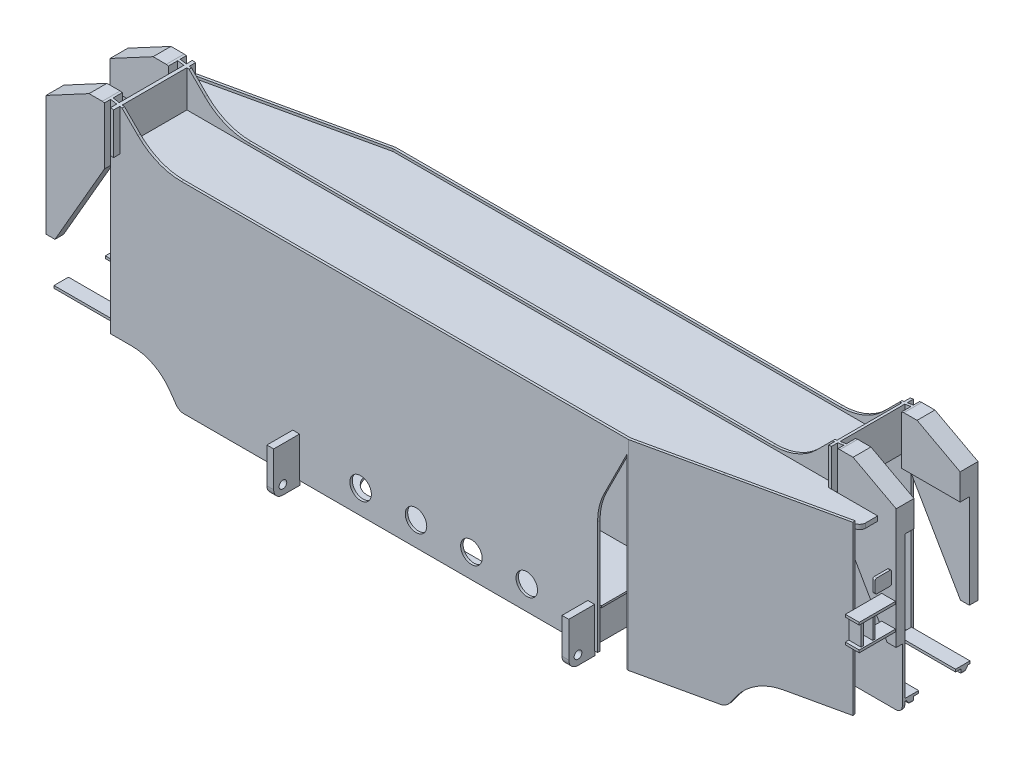
SolidWorks part; units mm, degrees
ref_plane "正面" through (0, 0, 0) normal (0, 0, 1) x (1, 0, 0)
ref_plane "平面" through (0, 0, 0) normal (0, 1, 0) x (1, 0, 0)
ref_plane "右側面" through (0, 0, 0) normal (1, 0, 0) x (0, 0, -1)
ref_plane "平面1" through (0, 0, 238) normal (0, 0, 1) x (1, 0, 0)
sketch "ｽｹｯﾁ2" plane through (0, 0, 238) normal (0, 0, 1) x (1, 0, 0)
  line L0 (20, 120) -> (259.781, 119.9998)
  line L1 (382.7741, 55.8641) -> (403.0452, 26.8271)
  line L2 (427.644, 13.9998) -> (2117.356, 13.9998)
  line L3 (2141.9548, 26.8271) -> (2162.2259, 55.8641)
  line L4 (2285.219, 119.9998) -> (2525, 120)
  line L5 (2545, 140) -> (2545, 315.36)
  line L6 (2545, 315.36) -> (2545, 706)
  line L7 (2545, 706) -> (2405, 781)
  line L8 (2405, 781) -> (2362, 781)
  line L9 (2362, 781) -> (2318, 774)
  line L10 (2318, 774) -> (2266.5789, 722.5791)
  line L11 (2125.157, 663.9999) -> (419.843, 663.9999)
  line L12 (278.4211, 722.5791) -> (227, 774)
  line L13 (227, 774) -> (183, 781)
  line L14 (183, 781) -> (140, 781)
  line L15 (140, 781) -> (0, 706)
  line L16 (0, 706) -> (0, 315.36)
  line L17 (0, 315.36) -> (0, 140)
  arc A0 (0, 140) -> (20, 120) centre (20, 140) ccw
  arc A1 (259.781, 119.9998) -> (382.7741, 55.8641) centre (259.781, -30) cw
  arc A2 (403.0452, 26.8271) -> (427.644, 13.9998) centre (427.644, 44) ccw
  arc A3 (2117.356, 13.9998) -> (2141.9548, 26.8271) centre (2117.356, 44) ccw
  arc A4 (2162.2259, 55.8641) -> (2285.219, 119.9998) centre (2285.219, -30) cw
  arc A5 (2525, 120) -> (2545, 140) centre (2525, 140) ccw
  arc A6 (2266.5789, 722.5791) -> (2125.157, 663.9999) centre (2125.157, 864) cw
  arc A7 (419.843, 663.9999) -> (278.4211, 722.5791) centre (419.843, 864) cw
extrude "ﾎﾞｽ - 押し出し1" add sketch "ｽｹｯﾁ2" along normal blind 8
sketch "ｽｹｯﾁ3" plane through (0, 0, 238) normal (0, 0, 1) x (1, 0, 0)
  line L0 (1072.5, 297) -> (1472.5, 297)
  line L1 (1472.5, 497) -> (1072.5, 497)
  circle A0 centre (972.5, 92) radius 35
  circle A1 centre (1272.5, 92) radius 35
  circle A2 centre (1572.5, 92) radius 35
  arc A3 (1472.5, 297) -> (1572.5, 397) centre (1472.5, 397) ccw
  arc A4 (1572.5, 397) -> (1472.5, 497) centre (1472.5, 397) ccw
  arc A5 (1072.5, 497) -> (972.5, 397) centre (1072.5, 397) ccw
  arc A6 (972.5, 397) -> (1072.5, 297) centre (1072.5, 397) ccw
  circle A7 centre (50, 499) radius 20.25
  circle A8 centre (2495, 499) radius 20.25
  circle A9 centre (27, 401.5) radius 10.5
  circle A10 centre (2518, 401.5) radius 10.5
sketch "ｽｹｯﾁ4" plane through (0, 0, 238) normal (0, 0, 1) x (1, 0, 0)
  line L0 (1072.5, 297) -> (1472.5, 297)
  line L1 (1472.5, 497) -> (1072.5, 497)
  circle A0 centre (972.5, 92) radius 35
  circle A1 centre (1272.5, 92) radius 35
  circle A2 centre (1572.5, 92) radius 35
  arc A3 (1472.5, 297) -> (1572.5, 397) centre (1472.5, 397) ccw
  arc A4 (1572.5, 397) -> (1472.5, 497) centre (1472.5, 397) ccw
  arc A5 (1072.5, 497) -> (972.5, 397) centre (1072.5, 397) ccw
  arc A6 (972.5, 397) -> (1072.5, 297) centre (1072.5, 397) ccw
  circle A7 centre (50, 499) radius 20.25
  circle A8 centre (2495, 499) radius 20.25
  circle A9 centre (27, 401.5) radius 10.5
  circle A10 centre (2518, 401.5) radius 10.5
extrude "ｶｯﾄ - 押し出し2" cut sketch "ｽｹｯﾁ4" along normal blind 8
ref_plane "平面2" through (0, 0, 20) normal (0, 0, 1) x (1, 0, 0)
sketch "ｽｹｯﾁ6" plane through (0, 0, 20) normal (0, 0, 1) x (1, 0, 0)
  line L0 (772.5, 14) -> (2117.356, 13.9998)
  line L1 (2141.9548, 26.8271) -> (2162.2259, 55.8641)
  line L2 (2285.219, 119.9998) -> (2355, 120)
  line L3 (2355, 120) -> (2355, 779.8864)
  line L4 (2355, 779.8864) -> (2318, 774)
  line L5 (2318, 774) -> (2266.5789, 722.5791)
  line L6 (2125.157, 663.9999) -> (672.5, 664)
  line L7 (672.5, 664) -> (672.5, 629)
  line L8 (672.5, 629) -> (751.3851, 471.2291)
  line L9 (772.4999, 381.786) -> (772.5, 14)
  arc A0 (2117.356, 13.9998) -> (2141.9548, 26.8271) centre (2117.356, 44) ccw
  arc A1 (2162.2259, 55.8641) -> (2285.219, 119.9998) centre (2285.219, -30) cw
  arc A2 (2266.5789, 722.5791) -> (2125.157, 663.9999) centre (2125.157, 864) cw
  arc A3 (751.3851, 471.2291) -> (772.4999, 381.786) centre (572.5, 381.786) cw
extrude "ﾎﾞｽ - 押し出し2" add sketch "ｽｹｯﾁ6" along normal blind 8
sketch "ｽｹｯﾁ7" plane through (0, 0, 20) normal (0, 0, 1) x (1, 0, 0)
  circle A0 centre (1002.5, 92) radius 35
  circle A1 centre (1182.5, 92) radius 35
  circle A2 centre (1362.5, 92) radius 35
  circle A3 centre (1542.5, 92) radius 35
sketch "ｽｹｯﾁ8" plane through (0, 0, 20) normal (0, 0, 1) x (1, 0, 0)
  circle A0 centre (1002.5, 92) radius 35
  circle A1 centre (1182.5, 92) radius 35
  circle A2 centre (1362.5, 92) radius 35
  circle A3 centre (1542.5, 92) radius 35
extrude "ｶｯﾄ - 押し出し4" cut sketch "ｽｹｯﾁ8" along normal blind 8
ref_plane "平面3" through (0, 0, 456) normal (0, 0, 1) x (1, 0, 0)
sketch "ｽｹｯﾁ10" plane through (0, 0, 456) normal (0, 0, 1) x (1, 0, 0)
  line L0 (1772.5, 14) -> (1772.5001, 381.786)
  line L1 (1793.6149, 471.2291) -> (1872.5, 629)
  line L2 (1872.5, 629) -> (1872.5, 664)
  line L3 (1872.5, 664) -> (419.843, 663.9999)
  line L4 (278.4211, 722.5791) -> (227, 774)
  line L5 (227, 774) -> (190, 779.8864)
  line L6 (190, 779.8864) -> (190, 120)
  line L7 (190, 120) -> (259.781, 119.9998)
  line L8 (382.7741, 55.8641) -> (403.0452, 26.8271)
  line L9 (427.644, 13.9998) -> (1772.5, 14)
  arc A0 (1772.5001, 381.786) -> (1793.6149, 471.2291) centre (1972.5, 381.786) cw
  arc A1 (419.843, 663.9999) -> (278.4211, 722.5791) centre (419.843, 864) cw
  arc A2 (259.781, 119.9998) -> (382.7741, 55.8641) centre (259.781, -30) cw
  arc A3 (403.0452, 26.8271) -> (427.644, 13.9998) centre (427.644, 44) ccw
extrude "ﾎﾞｽ - 押し出し3" add sketch "ｽｹｯﾁ10" along normal blind 8
sketch "ｽｹｯﾁ11" plane through (0, 0, 456) normal (0, 0, 1) x (1, 0, 0)
  circle A0 centre (1002.5, 92) radius 35
  circle A1 centre (1182.5, 92) radius 35
  circle A2 centre (1362.5, 92) radius 35
  circle A3 centre (1542.5, 92) radius 35
sketch "ｽｹｯﾁ12" plane through (0, 0, 456) normal (0, 0, 1) x (1, 0, 0)
  circle A0 centre (1002.5, 92) radius 35
  circle A1 centre (1182.5, 92) radius 35
  circle A2 centre (1362.5, 92) radius 35
  circle A3 centre (1542.5, 92) radius 35
extrude "ｶｯﾄ - 押し出し6" cut sketch "ｽｹｯﾁ12" along normal blind 8
ref_plane "平面4" through (0, 14, 0) normal (0, 1, 0) x (1, 0, 0)
sketch "ｽｹｯﾁ14" plane through (0, 14, 0) normal (0, 1, 0) x (1, 0, 0)
  line L0 (678.3594, -26.7085) -> (75.7, -159.54)
  line L1 (75.7, -159.54) -> (73.9781, -151.7275)
  line L2 (73.9781, -151.7275) -> (671.6288, -20)
  line L3 (671.6288, -20) -> (676.8807, -20)
  line L4 (676.8807, -20) -> (678.3594, -26.7085)
extrude "ﾎﾞｽ - 押し出し4" add sketch "ｽｹｯﾁ14" along normal blind 650
sketch "ｽｹｯﾁ15" plane through (0, 14, 0) normal (0, 1, 0) x (1, 0, 0)
  line L0 (1866.6406, -457.2915) -> (2469.3, -324.46)
  line L1 (2469.3, -324.46) -> (2471.0219, -332.2725)
  line L2 (2471.0219, -332.2725) -> (1873.3712, -464)
  line L3 (1873.3712, -464) -> (1868.1193, -464)
  line L4 (1868.1193, -464) -> (1866.6406, -457.2915)
extrude "ﾎﾞｽ - 押し出し5" add sketch "ｽｹｯﾁ15" along normal blind 650
ref_plane "平面5" through (0, 641, 0) normal (0, 1, 0) x (1, 0, 0)
sketch "ｽｹｯﾁ17" plane through (0, 641, 0) normal (0, 1, 0) x (1, 0, 0)
  line L0 (672.5, -28) -> (75.7206, -159.5325)
  line L1 (59.9974, -179.072) -> (60, -218)
  line L2 (60, -218) -> (220, -218)
  line L3 (220, -218) -> (220, -238)
  line L4 (220, -238) -> (2325, -238)
  line L5 (2325, -238) -> (2325, -28)
  line L6 (2325, -28) -> (672.5, -28)
  arc A0 (75.7206, -159.5325) -> (59.9974, -179.072) centre (80, -179.072) ccw
extrude "ﾎﾞｽ - 押し出し6" add sketch "ｽｹｯﾁ17" along normal blind 15
sketch "ｽｹｯﾁ18" plane through (0, 641, 0) normal (0, 1, 0) x (1, 0, 0)
  line L0 (1872.5, -456) -> (2469.2794, -324.4675)
  line L1 (2485.0026, -304.928) -> (2485, -266)
  line L2 (2485, -266) -> (2325, -266)
  line L3 (2325, -266) -> (2325, -246)
  line L4 (2325, -246) -> (220, -246)
  line L5 (220, -246) -> (220, -456)
  line L6 (220, -456) -> (1872.5, -456)
  arc A0 (2469.2794, -324.4675) -> (2485.0026, -304.928) centre (2465, -304.928) ccw
extrude "ﾎﾞｽ - 押し出し7" add sketch "ｽｹｯﾁ18" along normal blind 15
ref_plane "平面6" through (0, 22, 0) normal (0, 1, 0) x (1, 0, 0)
sketch "ｽｹｯﾁ20" plane through (0, 22, 0) normal (0, 1, 0) x (1, 0, 0)
  line L0 (804, -28) -> (2098.5, -28)
  line L1 (2098.5, -28) -> (2098.5, -238)
  line L2 (2098.5, -238) -> (804, -238)
  line L3 (804, -238) -> (804, -28)
extrude "ﾎﾞｽ - 押し出し8" add sketch "ｽｹｯﾁ20" along normal blind 8
sketch "ｽｹｯﾁ21" plane through (0, 22, 0) normal (0, 1, 0) x (1, 0, 0)
  line L0 (1202, -73) -> (1342, -73)
  line L1 (1342, -193) -> (1202, -193)
  circle A0 centre (972, -133) radius 60
  circle A1 centre (1572, -133) radius 60
  circle A2 centre (1942, -133) radius 60
  arc A3 (1342, -73) -> (1402, -133) centre (1342, -133) cw
  arc A4 (1402, -133) -> (1342, -193) centre (1342, -133) cw
  arc A5 (1202, -193) -> (1142, -133) centre (1202, -133) cw
  arc A6 (1142, -133) -> (1202, -73) centre (1202, -133) cw
sketch "ｽｹｯﾁ22" plane through (0, 22, 0) normal (0, 1, 0) x (1, 0, 0)
  line L0 (1202, -73) -> (1342, -73)
  line L1 (1342, -193) -> (1202, -193)
  circle A0 centre (972, -133) radius 60
  circle A1 centre (1572, -133) radius 60
  circle A2 centre (1942, -133) radius 60
  arc A3 (1342, -73) -> (1402, -133) centre (1342, -133) cw
  arc A4 (1402, -133) -> (1342, -193) centre (1342, -133) cw
  arc A5 (1202, -193) -> (1142, -133) centre (1202, -133) cw
  arc A6 (1142, -133) -> (1202, -73) centre (1202, -133) cw
extrude "ｶｯﾄ - 押し出し8" cut sketch "ｽｹｯﾁ22" along normal blind 8
sketch "ｽｹｯﾁ23" plane through (0, 22, 0) normal (0, 1, 0) x (1, 0, 0)
  line L0 (446.5, -246) -> (1741, -246)
  line L1 (1741, -246) -> (1741, -456)
  line L2 (1741, -456) -> (446.5, -456)
  line L3 (446.5, -456) -> (446.5, -246)
extrude "ﾎﾞｽ - 押し出し9" add sketch "ｽｹｯﾁ23" along normal blind 8
sketch "ｽｹｯﾁ24" plane through (0, 22, 0) normal (0, 1, 0) x (1, 0, 0)
  line L0 (1203, -291) -> (1343, -291)
  line L1 (1343, -411) -> (1203, -411)
  circle A0 centre (603, -351) radius 60
  circle A1 centre (973, -351) radius 60
  circle A2 centre (1573, -351) radius 60
  arc A3 (1343, -291) -> (1403, -351) centre (1343, -351) cw
  arc A4 (1403, -351) -> (1343, -411) centre (1343, -351) cw
  arc A5 (1203, -411) -> (1143, -351) centre (1203, -351) cw
  arc A6 (1143, -351) -> (1203, -291) centre (1203, -351) cw
extrude "ｶｯﾄ - 押し出し9" cut sketch "ｽｹｯﾁ24" along normal blind 8
ref_plane "平面7" through (0, 138, 0) normal (0, 1, 0) x (1, 0, 0)
sketch "ｽｹｯﾁ26" plane through (0, 138, 0) normal (0, 1, 0) x (1, 0, 0)
  line L0 (768, -28) -> (1712, -28)
  line L1 (1712, -28) -> (1712, -238)
  line L2 (1712, -238) -> (768, -238)
  line L3 (768, -238) -> (768, -28)
extrude "ﾎﾞｽ - 押し出し10" add sketch "ｽｹｯﾁ26" along normal blind 6
sketch "ｽｹｯﾁ27" plane through (0, 138, 0) normal (0, 1, 0) x (1, 0, 0)
  line L0 (833, -246) -> (1777, -246)
  line L1 (1777, -246) -> (1777, -456)
  line L2 (1777, -456) -> (833, -456)
  line L3 (833, -456) -> (833, -246)
extrude "ﾎﾞｽ - 押し出し11" add sketch "ｽｹｯﾁ27" along normal blind 6
ref_plane "平面8" through (0, 0, 218) normal (0, 0, 1) x (1, 0, 0)
sketch "ｽｹｯﾁ29" plane through (0, 0, 218) normal (0, 0, 1) x (1, 0, 0)
  line L0 (0, 315.36) -> (29.1052, 315.36)
  line L1 (29.1052, 315.36) -> (190, 594.038)
  line L2 (190, 594.038) -> (190, 779.8864)
  line L3 (190, 779.8864) -> (183, 781)
  line L4 (183, 781) -> (140, 781)
  line L5 (140, 781) -> (0, 706)
  line L6 (0, 706) -> (0, 315.36)
extrude "ﾎﾞｽ - 押し出し12" add sketch "ｽｹｯﾁ29" along normal blind 20
ref_plane "平面9" through (0, 0, 464) normal (0, 0, 1) x (1, 0, 0)
sketch "ｽｹｯﾁ31" plane through (0, 0, 464) normal (0, 0, 1) x (1, 0, 0)
  line L0 (0, 315.36) -> (29.1052, 315.36)
  line L1 (29.1052, 315.36) -> (190, 594.038)
  line L2 (190, 594.038) -> (190, 779.8864)
  line L3 (190, 779.8864) -> (183, 781)
  line L4 (183, 781) -> (140, 781)
  line L5 (140, 781) -> (0, 706)
  line L6 (0, 706) -> (0, 315.36)
extrude "ﾎﾞｽ - 押し出し13" add sketch "ｽｹｯﾁ31" along normal blind 20
sketch "ｽｹｯﾁ32" plane through (0, 0, 0) normal (0, 0, 1) x (1, 0, 0)
  line L0 (2545, 315.36) -> (2545, 706)
  line L1 (2545, 706) -> (2405, 781)
  line L2 (2405, 781) -> (2362, 781)
  line L3 (2362, 781) -> (2355, 779.8864)
  line L4 (2355, 779.8864) -> (2355, 594.038)
  line L5 (2355, 594.038) -> (2515.8948, 315.36)
  line L6 (2515.8948, 315.36) -> (2545, 315.36)
extrude "ﾎﾞｽ - 押し出し14" add sketch "ｽｹｯﾁ32" along normal blind 20
ref_plane "平面10" through (0, 0, 246) normal (0, 0, 1) x (1, 0, 0)
sketch "ｽｹｯﾁ34" plane through (0, 0, 246) normal (0, 0, 1) x (1, 0, 0)
  line L0 (2545, 315.36) -> (2545, 706)
  line L1 (2545, 706) -> (2405, 781)
  line L2 (2405, 781) -> (2362, 781)
  line L3 (2362, 781) -> (2355, 779.8864)
  line L4 (2355, 779.8864) -> (2355, 594.038)
  line L5 (2355, 594.038) -> (2515.8948, 315.36)
  line L6 (2515.8948, 315.36) -> (2545, 315.36)
extrude "ﾎﾞｽ - 押し出し15" add sketch "ｽｹｯﾁ34" along normal blind 20
sketch "ｽｹｯﾁ35" plane through (0, 0, 20) normal (0, 0, 1) x (1, 0, 0)
  line L0 (2545, 315.36) -> (2545, 706)
  line L1 (2545, 706) -> (2405, 781)
  line L2 (2405, 781) -> (2362, 781)
  line L3 (2362, 781) -> (2355, 779.8864)
  line L4 (2355, 779.8864) -> (2355, 594.038)
  line L5 (2355, 594.038) -> (2515.8948, 315.36)
  line L6 (2515.8948, 315.36) -> (2545, 315.36)
extrude "ﾎﾞｽ - 押し出し16" add sketch "ｽｹｯﾁ35" along normal blind 8
sketch "ｽｹｯﾁ36" plane through (0, 0, 456) normal (0, 0, 1) x (1, 0, 0)
  line L0 (0, 315.36) -> (29.1052, 315.36)
  line L1 (29.1052, 315.36) -> (190, 594.038)
  line L2 (190, 594.038) -> (190, 779.8864)
  line L3 (190, 779.8864) -> (183, 781)
  line L4 (183, 781) -> (140, 781)
  line L5 (140, 781) -> (0, 706)
  line L6 (0, 706) -> (0, 315.36)
extrude "ﾎﾞｽ - 押し出し17" add sketch "ｽｹｯﾁ36" along normal blind 8
sketch "ｽｹｯﾁ37" plane through (0, 0, 246) normal (0, 0, 1) x (1, 0, 0)
  line L0 (0, 620.82) -> (190, 620.82)
  line L1 (190, 620.82) -> (190, 779.8864)
  line L2 (190, 779.8864) -> (183, 781)
  line L3 (183, 781) -> (140, 781)
  line L4 (140, 781) -> (0, 706)
  line L5 (0, 706) -> (0, 620.82)
extrude "ﾎﾞｽ - 押し出し18" add sketch "ｽｹｯﾁ37" along normal blind 30
ref_plane "平面11" through (0, 0, 426) normal (0, 0, 1) x (1, 0, 0)
sketch "ｽｹｯﾁ39" plane through (0, 0, 426) normal (0, 0, 1) x (1, 0, 0)
  line L0 (0, 620.82) -> (190, 620.82)
  line L1 (190, 620.82) -> (190, 779.8864)
  line L2 (190, 779.8864) -> (183, 781)
  line L3 (183, 781) -> (140, 781)
  line L4 (140, 781) -> (0, 706)
  line L5 (0, 706) -> (0, 620.82)
extrude "ﾎﾞｽ - 押し出し19" add sketch "ｽｹｯﾁ39" along normal blind 30
ref_plane "平面12" through (0, 0, 28) normal (0, 0, 1) x (1, 0, 0)
sketch "ｽｹｯﾁ41" plane through (0, 0, 28) normal (0, 0, 1) x (1, 0, 0)
  line L0 (2545, 620.82) -> (2545, 706)
  line L1 (2545, 706) -> (2405, 781)
  line L2 (2405, 781) -> (2362, 781)
  line L3 (2362, 781) -> (2355, 779.8864)
  line L4 (2355, 779.8864) -> (2355, 620.82)
  line L5 (2355, 620.82) -> (2545, 620.82)
extrude "ﾎﾞｽ - 押し出し20" add sketch "ｽｹｯﾁ41" along normal blind 30
ref_plane "平面13" through (0, 0, 208) normal (0, 0, 1) x (1, 0, 0)
sketch "ｽｹｯﾁ43" plane through (0, 0, 208) normal (0, 0, 1) x (1, 0, 0)
  line L0 (2545, 620.82) -> (2545, 706)
  line L1 (2545, 706) -> (2405, 781)
  line L2 (2405, 781) -> (2362, 781)
  line L3 (2362, 781) -> (2355, 779.8864)
  line L4 (2355, 779.8864) -> (2355, 620.82)
  line L5 (2355, 620.82) -> (2545, 620.82)
extrude "ﾎﾞｽ - 押し出し21" add sketch "ｽｹｯﾁ43" along normal blind 30
sketch "ｽｹｯﾁ44" plane through (0, 0, 0) normal (1, 0, 0) x (0, 0, -1)
  line L0 (-251.6, 150) -> (-450.4, 150)
  line L1 (-450.4, 150) -> (-450.4, 149)
  line L2 (-450.4, 149) -> (-442.698, 138)
  line L3 (-442.698, 138) -> (-259.302, 138)
  line L4 (-259.302, 138) -> (-251.6, 149)
  line L5 (-251.6, 149) -> (-251.6, 150)
extrude "ﾎﾞｽ - 押し出し22" add sketch "ｽｹｯﾁ44" along normal blind 346.3065
sketch "ｽｹｯﾁ45" plane through (0, 138, 0) normal (0, 1, 0) x (1, 0, 0)
  line L0 (-10, -273.771) -> (155, -273.771)
  line L1 (195, -313.771) -> (195, -388.229)
  line L2 (155, -428.229) -> (-10, -428.229)
  line L3 (-10, -428.229) -> (-10, -273.771)
  arc A0 (155, -273.771) -> (195, -313.771) centre (155, -313.771) cw
  arc A1 (195, -388.229) -> (155, -428.229) centre (155, -388.229) cw
sketch "ｽｹｯﾁ46" plane through (0, 138, 0) normal (0, 1, 0) x (1, 0, 0)
  line L0 (-10, -273.771) -> (155, -273.771)
  line L1 (195, -313.771) -> (195, -388.229)
  line L2 (155, -428.229) -> (-10, -428.229)
  line L3 (-10, -428.229) -> (-10, -273.771)
  arc A0 (155, -273.771) -> (195, -313.771) centre (155, -313.771) cw
  arc A1 (195, -388.229) -> (155, -428.229) centre (155, -388.229) cw
extrude "ｶｯﾄ - 押し出し11" cut sketch "ｽｹｯﾁ46" along normal blind 12
ref_plane "平面14" through (2545, 0, 0) normal (1, 0, 0) x (0, 0, -1)
sketch "ｽｹｯﾁ48" plane through (2545, 0, 0) normal (1, 0, 0) x (0, 0, -1)
  line L0 (-232.4, 150) -> (-232.4, 149)
  line L1 (-232.4, 149) -> (-224.698, 138)
  line L2 (-224.698, 138) -> (-41.302, 138)
  line L3 (-41.302, 138) -> (-33.6, 149)
  line L4 (-33.6, 149) -> (-33.6, 150)
  line L5 (-33.6, 150) -> (-232.4, 150)
extrude "ﾎﾞｽ - 押し出し23" add sketch "ｽｹｯﾁ48" against normal blind 346.3065
sketch "ｽｹｯﾁ49" plane through (0, 138, 0) normal (0, 1, 0) x (1, 0, 0)
  line L0 (2555, -210.229) -> (2390, -210.229)
  line L1 (2350, -170.229) -> (2350, -95.771)
  line L2 (2390, -55.771) -> (2555, -55.771)
  line L3 (2555, -55.771) -> (2555, -210.229)
  arc A0 (2390, -210.229) -> (2350, -170.229) centre (2390, -170.229) cw
  arc A1 (2350, -95.771) -> (2390, -55.771) centre (2390, -95.771) cw
extrude "ｶｯﾄ - 押し出し12" cut sketch "ｽｹｯﾁ49" along normal blind 12
ref_plane "平面15" through (0, 150, 0) normal (0, 1, 0) x (1, 0, 0)
sketch "ｽｹｯﾁ51" plane through (0, 150, 0) normal (0, 1, 0) x (1, 0, 0)
  line L0 (0, -244) -> (190, -244)
  line L1 (190, -244) -> (190, -291)
  line L2 (190, -291) -> (0, -291)
  line L3 (0, -291) -> (0, -244)
  line L4 (0, -411) -> (190, -411)
  line L5 (190, -411) -> (190, -458)
  line L6 (190, -458) -> (0, -458)
  line L7 (0, -458) -> (0, -411)
  line L8 (215.708, -244) -> (833, -244)
  line L9 (833, -244) -> (833, -291)
  line L10 (833, -291) -> (215.708, -291)
  line L11 (215.708, -291) -> (215.708, -244)
  line L12 (215.708, -411) -> (833, -411)
  line L13 (833, -411) -> (833, -458)
  line L14 (833, -458) -> (215.708, -458)
  line L15 (215.708, -458) -> (215.708, -411)
extrude "ﾎﾞｽ - 押し出し24" add sketch "ｽｹｯﾁ51" along normal blind 8
sketch "ｽｹｯﾁ52" plane through (0, 150, 0) normal (0, 1, 0) x (1, 0, 0)
  line L0 (1712, -193) -> (2329.292, -193)
  line L1 (2329.292, -193) -> (2329.292, -240)
  line L2 (2329.292, -240) -> (1712, -240)
  line L3 (1712, -240) -> (1712, -193)
  line L4 (1712, -26) -> (2329.292, -26)
  line L5 (2329.292, -26) -> (2329.292, -73)
  line L6 (2329.292, -73) -> (1712, -73)
  line L7 (1712, -73) -> (1712, -26)
  line L8 (2355, -193) -> (2545, -193)
  line L9 (2545, -193) -> (2545, -240)
  line L10 (2545, -240) -> (2355, -240)
  line L11 (2355, -240) -> (2355, -193)
  line L12 (2355, -26) -> (2545, -26)
  line L13 (2545, -26) -> (2545, -73)
  line L14 (2545, -73) -> (2355, -73)
  line L15 (2355, -73) -> (2355, -26)
extrude "ﾎﾞｽ - 押し出し25" add sketch "ｽｹｯﾁ52" along normal blind 8
ref_plane "平面16" through (1771.5, 0, 0) normal (1, 0, 0) x (0, 0, -1)
sketch "ｽｹｯﾁ54" plane through (1771.5, 0, 0) normal (1, 0, 0) x (0, 0, -1)
  line L0 (-28, 30) -> (-40.32, 29.97)
  line L1 (-40.32, 29.97) -> (-63.75, 129.12)
  line L2 (-63.75, 129.12) -> (-53.54, 138)
  line L3 (-53.54, 138) -> (-28, 30)
extrude "ﾎﾞｽ - 押し出し26" add sketch "ｽｹｯﾁ54" along normal blind 319
sketch "ｽｹｯﾁ55" plane through (1771.5, 0, 0) normal (1, 0, 0) x (0, 0, -1)
  line L0 (-212.46, 138) -> (-202.25, 129.12)
  line L1 (-202.25, 129.12) -> (-225.68, 29.97)
  line L2 (-225.68, 29.97) -> (-238, 30)
  line L3 (-238, 30) -> (-212.46, 138)
extrude "ﾎﾞｽ - 押し出し27" add sketch "ｽｹｯﾁ55" along normal blind 319
ref_plane "平面17" through (454.5, 0, 0) normal (1, 0, 0) x (0, 0, -1)
sketch "ｽｹｯﾁ57" plane through (454.5, 0, 0) normal (1, 0, 0) x (0, 0, -1)
  line L0 (-430.46, 138) -> (-420.25, 129.12)
  line L1 (-420.25, 129.12) -> (-443.68, 29.97)
  line L2 (-443.68, 29.97) -> (-456, 30)
  line L3 (-456, 30) -> (-430.46, 138)
extrude "ﾎﾞｽ - 押し出し28" add sketch "ｽｹｯﾁ57" along normal blind 319
sketch "ｽｹｯﾁ58" plane through (454.5, 0, 0) normal (1, 0, 0) x (0, 0, -1)
  line L0 (-246, 30) -> (-258.32, 29.97)
  line L1 (-258.32, 29.97) -> (-281.75, 129.12)
  line L2 (-281.75, 129.12) -> (-271.54, 138)
  line L3 (-271.54, 138) -> (-246, 30)
extrude "ﾎﾞｽ - 押し出し29" add sketch "ｽｹｯﾁ58" along normal blind 319
sketch "ｽｹｯﾁ59" plane through (0, 0, 0) normal (0, 0, 1) x (1, 0, 0)
  line L0 (-80, -80) -> (2625, -80)
  line L1 (2625, -80) -> (2625, 860)
  line L2 (2625, 860) -> (-80, 860)
  line L3 (-80, 860) -> (-80, -80)
  line L4 (20, 120) -> (259.781, 119.9998)
  line L5 (382.7741, 55.8641) -> (403.0452, 26.8271)
  line L6 (427.644, 13.9998) -> (2117.356, 13.9998)
  line L7 (2141.9548, 26.8271) -> (2162.2259, 55.8641)
  line L8 (2285.219, 119.9998) -> (2525, 120)
  line L9 (2545, 140) -> (2545, 315.36)
  line L10 (2545, 315.36) -> (2545, 706)
  line L11 (2545, 706) -> (2405, 781)
  line L12 (2405, 781) -> (2362, 781)
  line L13 (2362, 781) -> (2318, 774)
  line L14 (2318, 774) -> (2266.5789, 722.5791)
  line L15 (2125.157, 663.9999) -> (419.843, 663.9999)
  line L16 (278.4211, 722.5791) -> (227, 774)
  line L17 (227, 774) -> (183, 781)
  line L18 (183, 781) -> (140, 781)
  line L19 (140, 781) -> (0, 706)
  line L20 (0, 706) -> (0, 315.36)
  line L21 (0, 315.36) -> (0, 140)
  arc A0 (0, 140) -> (20, 120) centre (20, 140) ccw
  arc A1 (259.781, 119.9998) -> (382.7741, 55.8641) centre (259.781, -30) cw
  arc A2 (403.0452, 26.8271) -> (427.644, 13.9998) centre (427.644, 44) ccw
  arc A3 (2117.356, 13.9998) -> (2141.9548, 26.8271) centre (2117.356, 44) ccw
  arc A4 (2162.2259, 55.8641) -> (2285.219, 119.9998) centre (2285.219, -30) cw
  arc A5 (2525, 120) -> (2545, 140) centre (2525, 140) ccw
  arc A6 (2266.5789, 722.5791) -> (2125.157, 663.9999) centre (2125.157, 864) cw
  arc A7 (419.843, 663.9999) -> (278.4211, 722.5791) centre (419.843, 864) cw
sketch "ｽｹｯﾁ60" plane through (0, 0, 0) normal (0, 0, 1) x (1, 0, 0)
  line L0 (-80, -80) -> (2625, -80)
  line L1 (2625, -80) -> (2625, 860)
  line L2 (2625, 860) -> (-80, 860)
  line L3 (-80, 860) -> (-80, -80)
  line L4 (20, 120) -> (259.781, 119.9998)
  line L5 (382.7741, 55.8641) -> (403.0452, 26.8271)
  line L6 (427.644, 13.9998) -> (2117.356, 13.9998)
  line L7 (2141.9548, 26.8271) -> (2162.2259, 55.8641)
  line L8 (2285.219, 119.9998) -> (2525, 120)
  line L9 (2545, 140) -> (2545, 315.36)
  line L10 (2545, 315.36) -> (2545, 706)
  line L11 (2545, 706) -> (2405, 781)
  line L12 (2405, 781) -> (2362, 781)
  line L13 (2362, 781) -> (2318, 774)
  line L14 (2318, 774) -> (2266.5789, 722.5791)
  line L15 (2125.157, 663.9999) -> (419.843, 663.9999)
  line L16 (278.4211, 722.5791) -> (227, 774)
  line L17 (227, 774) -> (183, 781)
  line L18 (183, 781) -> (140, 781)
  line L19 (140, 781) -> (0, 706)
  line L20 (0, 706) -> (0, 315.36)
  line L21 (0, 315.36) -> (0, 140)
  arc A0 (0, 140) -> (20, 120) centre (20, 140) ccw
  arc A1 (259.781, 119.9998) -> (382.7741, 55.8641) centre (259.781, -30) cw
  arc A2 (403.0452, 26.8271) -> (427.644, 13.9998) centre (427.644, 44) ccw
  arc A3 (2117.356, 13.9998) -> (2141.9548, 26.8271) centre (2117.356, 44) ccw
  arc A4 (2162.2259, 55.8641) -> (2285.219, 119.9998) centre (2285.219, -30) cw
  arc A5 (2525, 120) -> (2545, 140) centre (2525, 140) ccw
  arc A6 (2266.5789, 722.5791) -> (2125.157, 663.9999) centre (2125.157, 864) cw
  arc A7 (419.843, 663.9999) -> (278.4211, 722.5791) centre (419.843, 864) cw
extrude "ｶｯﾄ - 押し出し14" cut sketch "ｽｹｯﾁ60" along normal blind 600
ref_plane "平面18" through (782, 0, 0) normal (1, 0, 0) x (0, 0, -1)
sketch "ｽｹｯﾁ62" plane through (782, 0, 0) normal (1, 0, 0) x (0, 0, -1)
  line L0 (-26, 29) -> (-240, 29)
  line L1 (-240, 29) -> (-240, 138)
  line L2 (-240, 138) -> (-26, 138)
  line L3 (-26, 138) -> (-26, 29)
  line L4 (-244, 29) -> (-458, 29)
  line L5 (-458, 29) -> (-458, 138)
  line L6 (-458, 138) -> (-244, 138)
  line L7 (-244, 138) -> (-244, 29)
  line L8 (-462, 0) -> (-518, 0)
  line L9 (-548, 30) -> (-548, 145)
  line L10 (-548, 145) -> (-462, 145)
  line L11 (-462, 145) -> (-462, 0)
  arc A0 (-518, 0) -> (-548, 30) centre (-518, 30) cw
extrude "ﾎﾞｽ - 押し出し30" add sketch "ｽｹｯﾁ62" along normal blind 22
sketch "ｽｹｯﾁ63" plane through (782, 0, 0) normal (1, 0, 0) x (0, 0, -1)
  circle A0 centre (-518, 30) radius 12.5
sketch "ｽｹｯﾁ64" plane through (782, 0, 0) normal (1, 0, 0) x (0, 0, -1)
  circle A0 centre (-518, 30) radius 12.5
extrude "ｶｯﾄ - 押し出し16" cut sketch "ｽｹｯﾁ64" along normal blind 22
ref_plane "平面19" through (1741, 0, 0) normal (1, 0, 0) x (0, 0, -1)
sketch "ｽｹｯﾁ66" plane through (1741, 0, 0) normal (1, 0, 0) x (0, 0, -1)
  line L0 (-26, 29) -> (-240, 29)
  line L1 (-240, 29) -> (-240, 138)
  line L2 (-240, 138) -> (-26, 138)
  line L3 (-26, 138) -> (-26, 29)
  line L4 (-244, 29) -> (-458, 29)
  line L5 (-458, 29) -> (-458, 138)
  line L6 (-458, 138) -> (-244, 138)
  line L7 (-244, 138) -> (-244, 29)
  line L8 (-462, 0) -> (-518, 0)
  line L9 (-548, 30) -> (-548, 145)
  line L10 (-548, 145) -> (-462, 145)
  line L11 (-462, 145) -> (-462, 0)
  arc A0 (-518, 0) -> (-548, 30) centre (-518, 30) cw
extrude "ﾎﾞｽ - 押し出し31" add sketch "ｽｹｯﾁ66" along normal blind 22
sketch "ｽｹｯﾁ67" plane through (1741, 0, 0) normal (1, 0, 0) x (0, 0, -1)
  circle A0 centre (-518, 30) radius 12.5
sketch "ｽｹｯﾁ68" plane through (1741, 0, 0) normal (1, 0, 0) x (0, 0, -1)
  circle A0 centre (-518, 30) radius 12.5
extrude "ｶｯﾄ - 押し出し18" cut sketch "ｽｹｯﾁ68" along normal blind 22
ref_plane "平面20" through (2, 0, 0) normal (1, 0, 0) x (0, 0, -1)
sketch "ｽｹｯﾁ70" plane through (2, 0, 0) normal (1, 0, 0) x (0, 0, -1)
  line L0 (-100, 358.5) -> (-218, 358.5)
  line L1 (-218, 358.5) -> (-218, 366.5)
  line L2 (-218, 366.5) -> (-100, 366.5)
  line L3 (-100, 366.5) -> (-100, 358.5)
  line L4 (-100, 436.5) -> (-218, 436.5)
  line L5 (-218, 436.5) -> (-218, 444.5)
  line L6 (-218, 444.5) -> (-100, 444.5)
  line L7 (-100, 444.5) -> (-100, 436.5)
extrude "ﾎﾞｽ - 押し出し32" add sketch "ｽｹｯﾁ70" along normal blind 45
ref_plane "平面21" through (7, 0, 0) normal (1, 0, 0) x (0, 0, -1)
sketch "ｽｹｯﾁ72" plane through (7, 0, 0) normal (1, 0, 0) x (0, 0, -1)
  line L0 (-111, 366.5) -> (-119, 366.5)
  line L1 (-119, 366.5) -> (-119, 436.5)
  line L2 (-119, 436.5) -> (-111, 436.5)
  line L3 (-111, 436.5) -> (-111, 366.5)
  line L4 (-149, 366.5) -> (-157, 366.5)
  line L5 (-157, 366.5) -> (-157, 436.5)
  line L6 (-157, 436.5) -> (-149, 436.5)
  line L7 (-149, 436.5) -> (-149, 366.5)
extrude "ﾎﾞｽ - 押し出し33" add sketch "ｽｹｯﾁ72" along normal blind 40
ref_plane "平面22" through (2498, 0, 0) normal (1, 0, 0) x (0, 0, -1)
sketch "ｽｹｯﾁ74" plane through (2498, 0, 0) normal (1, 0, 0) x (0, 0, -1)
  line L0 (-266, 358.5) -> (-384, 358.5)
  line L1 (-384, 358.5) -> (-384, 366.5)
  line L2 (-384, 366.5) -> (-266, 366.5)
  line L3 (-266, 366.5) -> (-266, 358.5)
  line L4 (-266, 436.5) -> (-384, 436.5)
  line L5 (-384, 436.5) -> (-384, 444.5)
  line L6 (-384, 444.5) -> (-266, 444.5)
  line L7 (-266, 444.5) -> (-266, 436.5)
extrude "ﾎﾞｽ - 押し出し34" add sketch "ｽｹｯﾁ74" along normal blind 45
sketch "ｽｹｯﾁ75" plane through (2498, 0, 0) normal (1, 0, 0) x (0, 0, -1)
  line L0 (-365, 366.5) -> (-373, 366.5)
  line L1 (-373, 366.5) -> (-373, 436.5)
  line L2 (-373, 436.5) -> (-365, 436.5)
  line L3 (-365, 436.5) -> (-365, 366.5)
  line L4 (-327, 366.5) -> (-335, 366.5)
  line L5 (-335, 366.5) -> (-335, 436.5)
  line L6 (-335, 436.5) -> (-327, 436.5)
  line L7 (-327, 436.5) -> (-327, 366.5)
extrude "ﾎﾞｽ - 押し出し35" add sketch "ｽｹｯﾁ75" along normal blind 40
ref_plane "平面23" through (15, 0, 0) normal (1, 0, 0) x (0, 0, -1)
sketch "ｽｹｯﾁ77" plane through (15, 0, 0) normal (1, 0, 0) x (0, 0, -1)
  line L0 (-170, 483) -> (-213, 483)
  line L1 (-218, 488) -> (-218, 523)
  line L2 (-213, 528) -> (-170, 528)
  line L3 (-165, 523) -> (-165, 488)
  arc A0 (-213, 483) -> (-218, 488) centre (-213, 488) cw
  arc A1 (-218, 523) -> (-213, 528) centre (-213, 523) cw
  arc A2 (-170, 528) -> (-165, 523) centre (-170, 523) cw
  arc A3 (-165, 488) -> (-170, 483) centre (-170, 488) cw
extrude "ﾎﾞｽ - 押し出し36" add sketch "ｽｹｯﾁ77" along normal blind 8
ref_plane "平面24" through (2522, 0, 0) normal (1, 0, 0) x (0, 0, -1)
sketch "ｽｹｯﾁ79" plane through (2522, 0, 0) normal (1, 0, 0) x (0, 0, -1)
  line L0 (-271, 483) -> (-314, 483)
  line L1 (-319, 488) -> (-319, 523)
  line L2 (-314, 528) -> (-271, 528)
  line L3 (-266, 523) -> (-266, 488)
  arc A0 (-314, 483) -> (-319, 488) centre (-314, 488) cw
  arc A1 (-319, 523) -> (-314, 528) centre (-314, 523) cw
  arc A2 (-271, 528) -> (-266, 523) centre (-271, 523) cw
  arc A3 (-266, 488) -> (-271, 483) centre (-271, 488) cw
extrude "ﾎﾞｽ - 押し出し37" add sketch "ｽｹｯﾁ79" along normal blind 8
sketch "ｽｹｯﾁ80" plane through (0, 0, 218) normal (0, 0, 1) x (1, 0, 0)
  line L0 (210, 641) -> (220, 641)
  line L1 (220, 641) -> (220, 775.1136)
  line L2 (220, 775.1136) -> (210, 776.7045)
  line L3 (210, 776.7045) -> (210, 641)
extrude "ﾎﾞｽ - 押し出し38" add sketch "ｽｹｯﾁ80" along normal blind 266
sketch "ｽｹｯﾁ81" plane through (0, 0, 0) normal (0, 0, 1) x (1, 0, 0)
  line L0 (2325, 641) -> (2335, 641)
  line L1 (2335, 641) -> (2335, 776.7045)
  line L2 (2335, 776.7045) -> (2325, 775.1136)
  line L3 (2325, 775.1136) -> (2325, 641)
extrude "ﾎﾞｽ - 押し出し39" add sketch "ｽｹｯﾁ81" along normal blind 266
ref_plane "平面25" through (0, 0, 257) normal (0, 0, 1) x (1, 0, 0)
sketch "ｽｹｯﾁ83" plane through (0, 0, 257) normal (0, 0, 1) x (1, 0, 0)
  line L0 (412.1531, 22.0886) -> (421.9829, 28.9714)
  line L1 (421.9829, 28.9714) -> (348.6229, 133.7414)
  line L2 (348.6229, 133.7414) -> (338.7931, 126.8586)
  line L3 (338.7931, 126.8586) -> (412.1531, 22.0886)
extrude "ﾎﾞｽ - 押し出し40" add sketch "ｽｹｯﾁ83" along normal blind 188
ref_plane "平面26" through (0, 0, 351) normal (0, 0, 1) x (1, 0, 0)
sketch "ｽｹｯﾁ85" plane through (0, 0, 351) normal (0, 0, 1) x (1, 0, 0)
  line L0 (359.9091, 63.5757) -> (400.8669, 92.2543)
  line L1 (400.8669, 92.2543) -> (377.924, 125.0205)
  line L2 (377.924, 125.0205) -> (336.9662, 96.3419)
  line L3 (336.9662, 96.3419) -> (359.9091, 63.5757)
  line L4 (359.9091, 63.5757) -> (400.8669, 92.2543) construction
revolve "ｶｯﾄ - 回転1" cut sketch "ｽｹｯﾁ85" angle 360 about L4
ref_plane "平面27" through (0, 0, 39) normal (0, 0, 1) x (1, 0, 0)
sketch "ｽｹｯﾁ87" plane through (0, 0, 39) normal (0, 0, 1) x (1, 0, 0)
  line L0 (2206.2069, 126.8586) -> (2196.3771, 133.7414)
  line L1 (2196.3771, 133.7414) -> (2123.0171, 28.9714)
  line L2 (2123.0171, 28.9714) -> (2132.8469, 22.0886)
  line L3 (2132.8469, 22.0886) -> (2206.2069, 126.8586)
extrude "ﾎﾞｽ - 押し出し41" add sketch "ｽｹｯﾁ87" along normal blind 188
ref_plane "平面28" through (0, 0, 133) normal (0, 0, 1) x (1, 0, 0)
sketch "ｽｹｯﾁ89" plane through (0, 0, 133) normal (0, 0, 1) x (1, 0, 0)
  line L0 (2185.0909, 63.5757) -> (2144.1331, 92.2543)
  line L1 (2144.1331, 92.2543) -> (2121.1902, 59.4881)
  line L2 (2121.1902, 59.4881) -> (2162.148, 30.8095)
  line L3 (2162.148, 30.8095) -> (2185.0909, 63.5757)
  line L4 (2185.0909, 63.5757) -> (2144.1331, 92.2543) construction
revolve "ｶｯﾄ - 回転2" cut sketch "ｽｹｯﾁ89" angle 360 about L4
